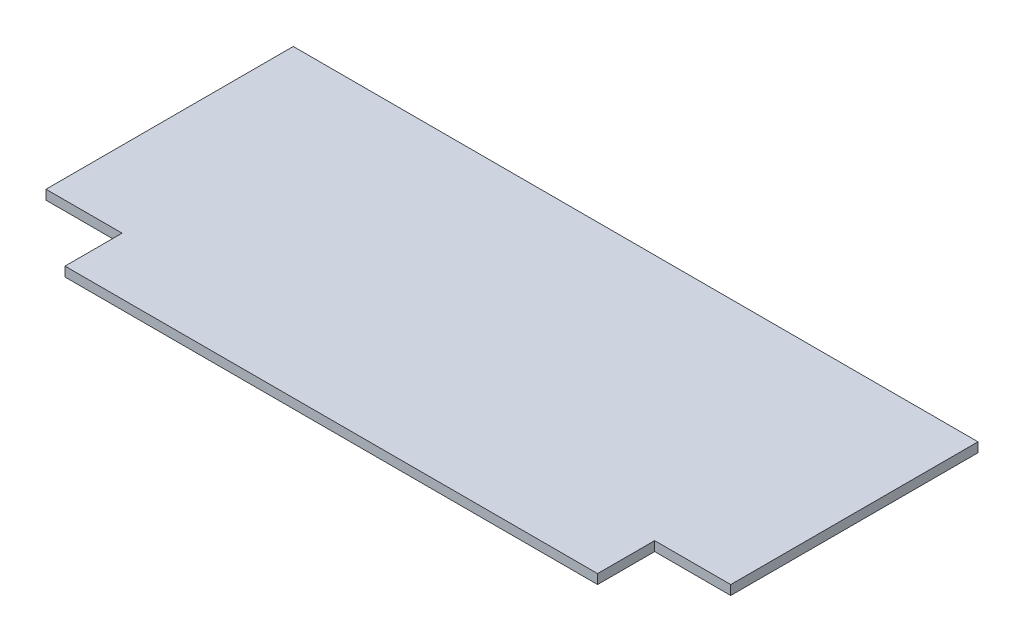
SolidWorks part; units mm, degrees
ref_plane "Front Plane" through (0, 0, 0) normal (0, 0, 1) x (1, 0, 0)
ref_plane "Top Plane" through (0, 0, 0) normal (0, 1, 0) x (1, 0, 0)
ref_plane "Right Plane" through (0, 0, 0) normal (1, 0, 0) x (0, 0, -1)
sketch "Sketch1" plane through (0, 0, 0) normal (0, 1, 0) x (1, 0, 0)
  line L1 (228.6, -101.6) -> (-228.6, -101.6)
  line L2 (228.6, -101.6) -> (228.6, 101.6)
  line L3 (228.6, 101.6) -> (-228.6, 101.6)
  line L4 (-228.6, -101.6) -> (-228.6, 101.6)
  line L5 (228.6, -101.6) -> (-228.6, 101.6) construction
  line L6 (228.6, 101.6) -> (-228.6, -101.6) construction
  point P0 (0, 0)
  dimension "D1" = 457.2
  dimension "D2" = 203.2
extrude "Boss-Extrude1" add sketch "Sketch1" along normal blind 6.35
sketch "Sketch2" plane through (0, 6.35, 0) normal (0, 1, 0) x (1, 0, 0)
  line L1 (-228.6, -101.6) -> (-177.8, -101.6)
  line L2 (-228.6, -101.6) -> (-228.6, -63.5)
  line L3 (-228.6, -63.5) -> (-177.8, -63.5)
  line L4 (-177.8, -101.6) -> (-177.8, -63.5)
  line L5 (228.6, -101.6) -> (177.8, -101.6)
  line L6 (228.6, -101.6) -> (228.6, -63.5)
  line L7 (228.6, -63.5) -> (177.8, -63.5)
  line L8 (177.8, -101.6) -> (177.8, -63.5)
  dimension "D1" = 50.8
  dimension "D2" = 38.1
  dimension "D3" = 38.1
  dimension "D4" = 50.8
extrude "Cut-Extrude1" cut sketch "Sketch2" against normal through all
